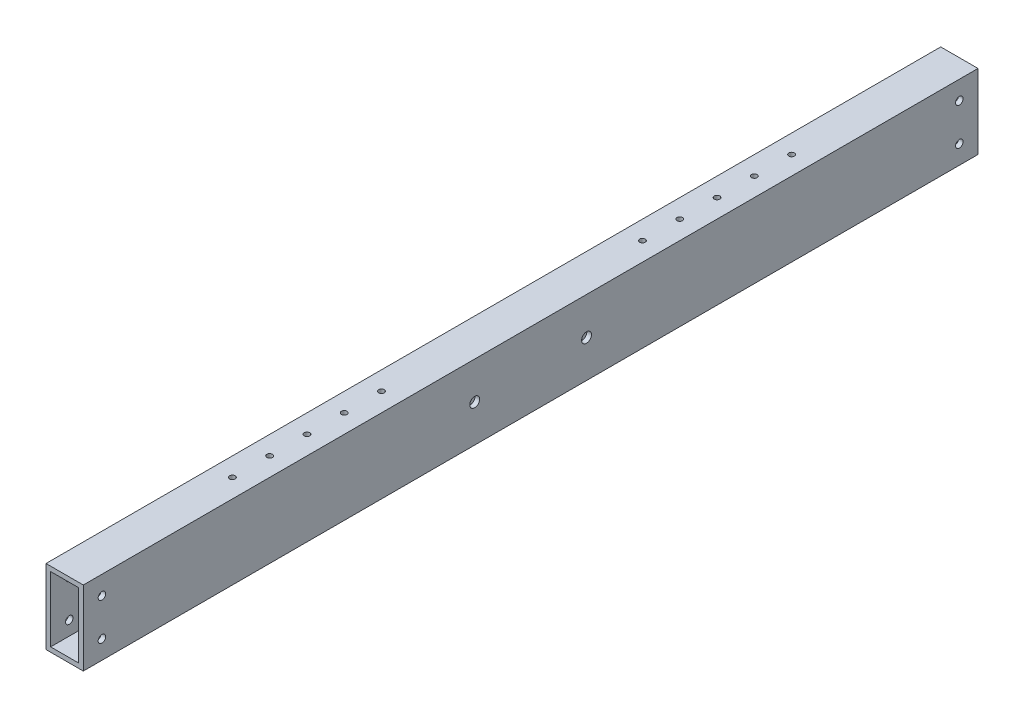
SolidWorks part; units mm, degrees
material "6061-T6 (SS)"
ref_plane "Front Plane" through (0, 0, 0) normal (0, 0, 1) x (1, 0, 0)
ref_plane "Top Plane" through (0, 0, 0) normal (0, 1, 0) x (1, 0, 0)
ref_plane "Right Plane" through (0, 0, 0) normal (1, 0, 0) x (0, 0, -1)
sketch "Sketch1" plane through (0, 0, 0) normal (0, 0, 1) x (1, 0, 0)
  line L0 (-9.525, 22.225) -> (9.525, 22.225)
  line L1 (-12.7, 25.4) -> (12.7, 25.4)
  line L2 (-12.7, 25.4) -> (-12.7, -25.4)
  line L3 (-12.7, -25.4) -> (12.7, -25.4)
  line L4 (12.7, 25.4) -> (12.7, -25.4)
  line L5 (-12.7, 25.4) -> (12.7, -25.4) construction
  line L6 (-12.7, -25.4) -> (12.7, 25.4) construction
  line L7 (9.525, 22.225) -> (9.525, -22.225)
  line L8 (-9.525, -22.225) -> (9.525, -22.225)
  line L9 (-9.525, 22.225) -> (-9.525, -22.225)
  point P0 (0, 0)
  dimension "D1" = 50.8
  dimension "D2" = 25.4
  dimension "D3" = 3.175
extrude "Boss-Extrude1" add sketch "Sketch1" along normal mid plane 609.6
hole_wizard "#10 Clearance Hole1" positions "Sketch4" profile "Sketch3" hole size "#10" standard "ANSI Inch" end condition through all
sketch "Sketch4" plane through (12.7, 0, 0) normal (1, 0, 0) x (0, 0, -1)
  line L0 (-304.8, 25.4) -> (304.8, 25.4) construction
  point P0 (-292.1, 12.7)
  point P13 (-292.1, -12.7)
  dimension "D2" = 12.7
  dimension "D1" = 2
sketch "Sketch3" plane through (12.7, 12.7, 292.1) normal (0, 1, 0) x (0, 0, -1)
  line L0 (0, 0) -> (0, 25.4)
  line L1 (0, 25.4) -> (2.5527, 25.4)
  line L2 (2.5527, 25.4) -> (2.5527, 0)
  line L5 (2.5527, 0) -> (0, 0)
  line L11 (0, -6.35) -> (0, 107.95) construction
  dimension "Thru Hole Dia." = 5.1054
  dimension "Thru Hole Depth" = 25.4
mirror "Mirror1" about plane through (0, 0, 0) normal (0, 0, 1) of "#10 Clearance Hole1"
hole_wizard "1/4 Clearance Hole2" positions "Sketch6" profile "Sketch5" hole size "1/4" standard "ANSI Inch" end condition through all
sketch "Sketch6" plane through (12.7, 0, 0) normal (1, 0, 0) x (0, 0, -1)
  line L0 (-38.1, 0) -> (38.1, 0) construction
  point P0 (-38.1, 0)
  point P2 (38.1, 0)
  dimension "D1" = 76.2
sketch "Sketch5" plane through (12.7, 0, 38.1) normal (0, 1, 0) x (0, 0, -1)
  line L0 (0, 0) -> (0, 25.4)
  line L1 (0, 25.4) -> (3.3782, 25.4)
  line L2 (3.3782, 25.4) -> (3.3782, 0)
  line L5 (3.3782, 0) -> (0, 0)
  line L11 (0, -6.35) -> (0, 107.95) construction
  dimension "Thru Hole Dia." = 6.7564
  dimension "Thru Hole Depth" = 25.4
sketch "Sketch7" plane through (0, 25.4, 0) normal (0, 1, 0) x (1, 0, 0)
  line L0 (-12.7, -304.8) -> (-12.7, 304.8) construction
  line L1 (12.7, 304.8) -> (-12.7, 304.8) construction
  circle A0 centre (0, 190.5) radius 1.905
  circle A1 centre (0, 165.1) radius 1.905
  circle A2 centre (0, 139.7) radius 1.905
  circle A3 centre (0, 114.3) radius 1.905
  circle A4 centre (0, 88.9) radius 1.905
  dimension "D1" = 3.81
  dimension "D2" = 12.7
  dimension "D3" = 114.3
  dimension "D4" = 5
extrude "Cut-Extrude1" cut sketch "Sketch7" against normal through all
mirror "Mirror2" about plane through (0, 0, 0) normal (0, 0, 1) of "Cut-Extrude1"
